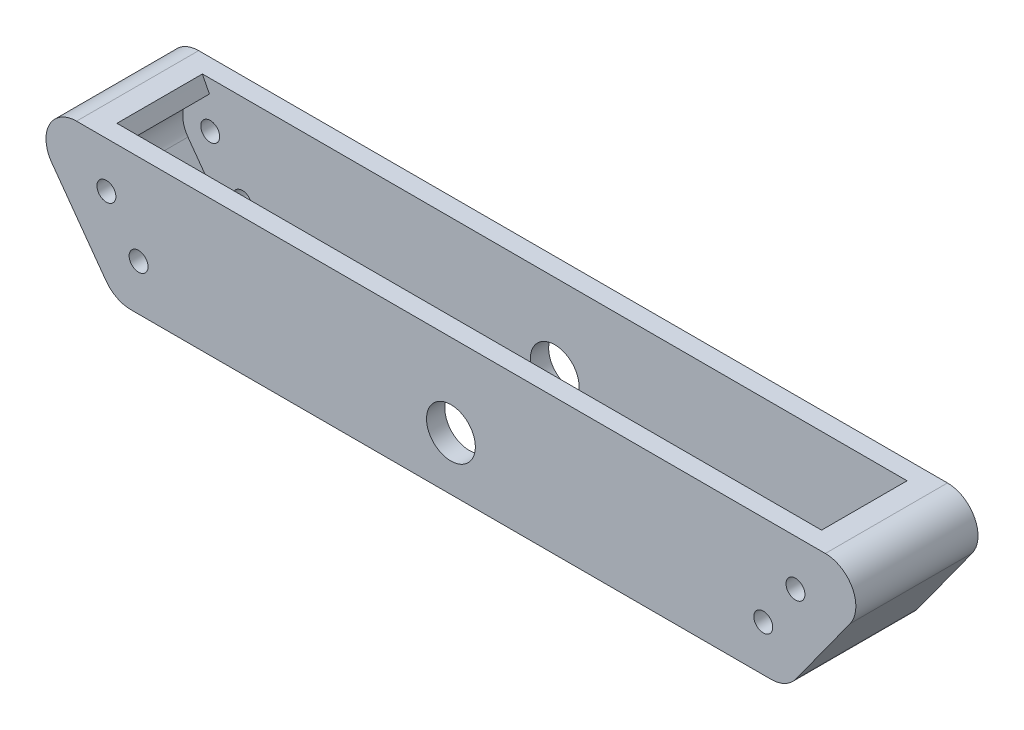
SolidWorks part; units mm, degrees
ref_plane "Front Plane" through (0, 0, 0) normal (0, 0, 1) x (1, 0, 0)
ref_plane "Top Plane" through (0, 0, 0) normal (0, 1, 0) x (1, 0, 0)
ref_plane "Right Plane" through (0, 0, 0) normal (1, 0, 0) x (0, 0, -1)
sketch "Sketch1" plane through (0, 0, 0) normal (0, 0, 1) x (1, 0, 0)
  line L0 (0, 0) -> (0, -62.5) construction
  line L1 (-71.0874, -27.7045) -> (0, -27.7045) construction
  line L2 (0, -50) -> (-54.9811, -50) construction
  line L3 (-54.9811, -50) -> (-71.0874, -27.7045) construction
  line L4 (-56.4171, -35.2045) -> (-51.1468, -42.5) construction
  line L5 (-71.0874, -27.7045) -> (-54.9811, -50)
  line L6 (-54.9811, -50) -> (-39.95, -50)
  line L7 (-71.0874, -27.7045) -> (-57.6928, -27.7045)
  line L8 (54.9811, -50) -> (39.95, -50)
  line L9 (71.0874, -27.7045) -> (54.9811, -50)
  line L10 (71.0874, -27.7045) -> (57.6928, -27.7045)
  line L11 (-58.7994, -31.3868) -> (-56.5441, -29.9795)
  line L12 (48.7646, -46.3177) -> (45.9424, -44.5566)
  line L13 (-56.4171, -35.2045) -> (0, 0) construction
  line L14 (-60.0649, -37.8397) -> (-54.7946, -45.1351)
  line L15 (-48.7646, -46.3177) -> (-45.9424, -44.5566)
  line L16 (60.0649, -37.8397) -> (54.7946, -45.1351)
  line L17 (58.7994, -31.3868) -> (56.5441, -29.9795)
  circle A0 centre (0, 0) radius 62.5 construction
  circle A2 centre (0, -41.25) radius 4
  circle A3 centre (-56.4171, -35.2045) radius 4 construction
  circle A4 centre (-51.1468, -42.5) radius 4 construction
  circle A5 centre (-56.4171, -35.2045) radius 1.55
  circle A6 centre (-51.1468, -42.5) radius 1.55
  circle A7 centre (0, -41.25) radius 15
  circle A8 centre (0, 0) radius 55.5 construction
  circle A9 centre (0, 0) radius 56.25 construction
  circle A10 centre (0, 0) radius 64 construction
  arc A11 (-57.6928, -27.7045) -> (-39.95, -50) centre (0, 0) ccw
  arc A12 (57.6928, -27.7045) -> (39.95, -50) centre (0, 0) cw
  circle A13 centre (51.1468, -42.5) radius 1.55
  circle A14 centre (56.4171, -35.2045) radius 1.55
  circle A15 centre (-56.4171, -35.2045) radius 4.5 construction
  arc A16 (-58.7994, -31.3868) -> (-60.0649, -37.8397) centre (-56.4171, -35.2045) ccw
  circle A17 centre (-51.1468, -42.5) radius 4.5 construction
  arc A18 (-48.7646, -46.3177) -> (-54.7946, -45.1351) centre (-51.1468, -42.5) cw
  arc A19 (48.7646, -46.3177) -> (54.7946, -45.1351) centre (51.1468, -42.5) ccw
  arc A20 (58.7994, -31.3868) -> (60.0649, -37.8397) centre (56.4171, -35.2045) cw
  point P26 (0, 0)
  dimension "D1" = 125
  dimension "D3" = 8
  dimension "D4" = 8
  dimension "D9" = 3.1
  dimension "D11" = 30
  dimension "D12" = 112.5
  dimension "D13" = 128
  dimension "D14" = 9
  dimension "D15" = 9
  dimension "D5" = 9
  dimension "D6" = 20
  dimension "D7" = 7.5
  dimension "D8" = 7.5
  dimension "D10" = 7.5
  dimension "D2" = 7
extrude "Boss-Extrude1" add sketch "Sketch1" along normal mid plane 14 contours A11 L7 L5 L6 A6 A5 | L10 A12 L8 L9 A13 A14 region at (-64.3901, -28.0875, 0) region at (47.4655, -49.617, 0)
sketch "Sketch2" plane through (0, 0, 7) normal (0, 0, 1) x (1, 0, 0)
  line L0 (-54.9811, -50) -> (54.9811, -50)
  line L1 (54.9811, -50) -> (71.0874, -27.7045)
  line L2 (71.0874, -27.7045) -> (-71.0874, -27.7045)
  line L3 (-71.0874, -27.7045) -> (-54.9811, -50)
  circle A0 centre (0, -41.25) radius 4 construction
  circle A1 centre (0, -41.25) radius 4
  circle A10 centre (-51.1468, -42.5) radius 1.55 construction
  circle A11 centre (-56.4171, -35.2045) radius 1.55 construction
  circle A12 centre (-51.1468, -42.5) radius 1.55
  circle A13 centre (-56.4171, -35.2045) radius 1.55
  circle A14 centre (56.4171, -35.2045) radius 1.55 construction
  circle A15 centre (51.1468, -42.5) radius 1.55 construction
  circle A16 centre (56.4171, -35.2045) radius 1.55
  circle A17 centre (51.1468, -42.5) radius 1.55
extrude "Boss-Extrude2" add sketch "Sketch2" along normal blind 3
mirror "Mirror2" about plane through (0, 0, 0) normal (0, 0, 1) of "Boss-Extrude2"
fillet "Fillet1" radius 5 4 edges at (-54.9811, -50, 0) (54.9811, -50, 0) (71.0874, -27.7045, 0) (-71.0874, -27.7045, 0)
fillet "Fillet2" radius 1 2 edges at (39.95, -50, 0) (-39.95, -50, 0)
equation "\"D12@Sketch1\"=75*1.5"
equation "\"D11@Sketch1\"=20*1.5"
